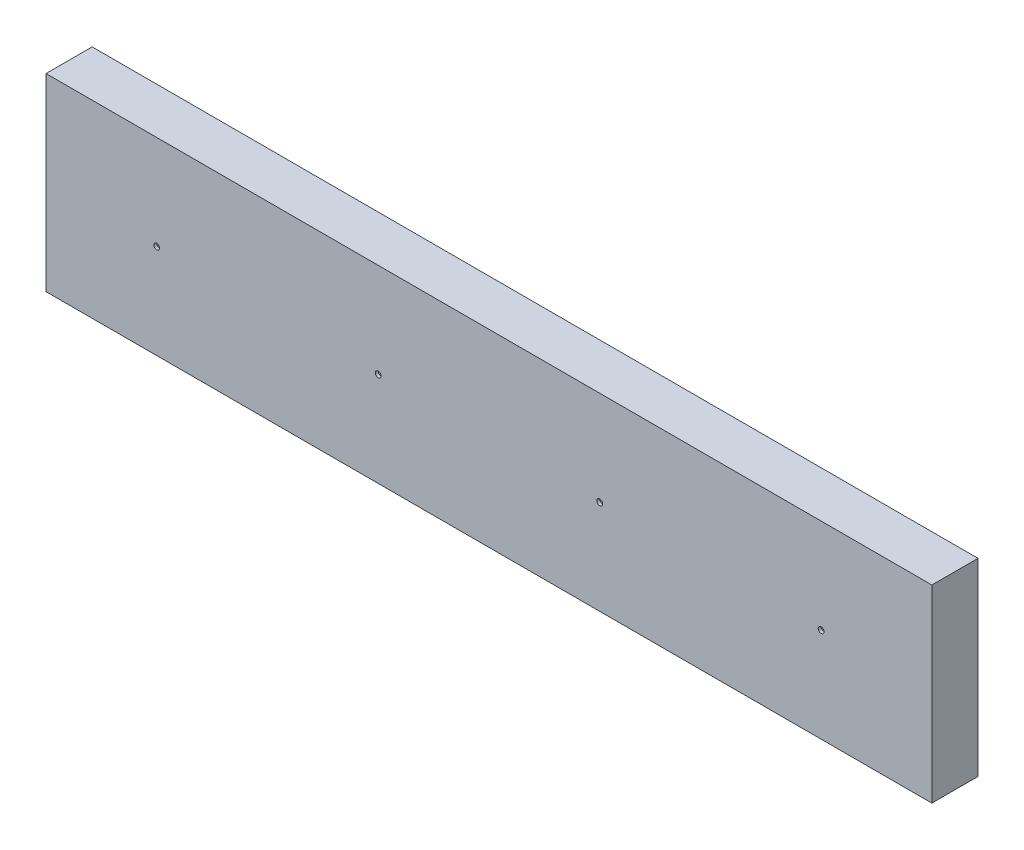
SolidWorks part; units mm, degrees
ref_plane "Front Plane" through (0, 0, 0) normal (0, 0, 1) x (1, 0, 0)
ref_plane "Top Plane" through (0, 0, 0) normal (0, 1, 0) x (1, 0, 0)
ref_plane "Right Plane" through (0, 0, 0) normal (1, 0, 0) x (0, 0, -1)
sketch "Sketch1" plane through (0, 0, 0) normal (0, 0, 1) x (1, 0, 0)
  line L1 (-152.4, 32.5) -> (152.4, 32.5)
  line L2 (-152.4, 32.5) -> (-152.4, -32.5)
  line L3 (-152.4, -32.5) -> (152.4, -32.5)
  line L4 (152.4, 32.5) -> (152.4, -32.5)
  line L5 (-152.4, 32.5) -> (152.4, -32.5) construction
  line L6 (-152.4, -32.5) -> (152.4, 32.5) construction
  point P0 (0, 0)
  dimension "D1" = 65
  dimension "D2" = 304.8
extrude "Boss-Extrude1" add sketch "Sketch1" along normal blind 15.875
sketch "Sketch2" plane through (0, 0, 15.875) normal (0, 0, 1) x (1, 0, 0)
  line L0 (0, 0) -> (0, -32.5) construction
  line L1 (-152.4, -32.5) -> (152.4, -32.5) construction
  circle A0 centre (-38.1, 0) radius 1
  circle A1 centre (-114.3, 0) radius 1
  circle A4 centre (114.3, 0) radius 1
  circle A5 centre (38.1, 0) radius 1
  point P4 (-76.6805, 22.6325)
  point P5 (0, 0)
  point P6 (101.9619, 1.9558)
  point P7 (-100.0089, -6.5)
  point P17 (0, 0)
  dimension "D2" = 76.2
  dimension "D3" = 2
  dimension "D1" = 76.2
extrude "Cut-Extrude1" cut sketch "Sketch2" against normal blind 1 and the other way through all
